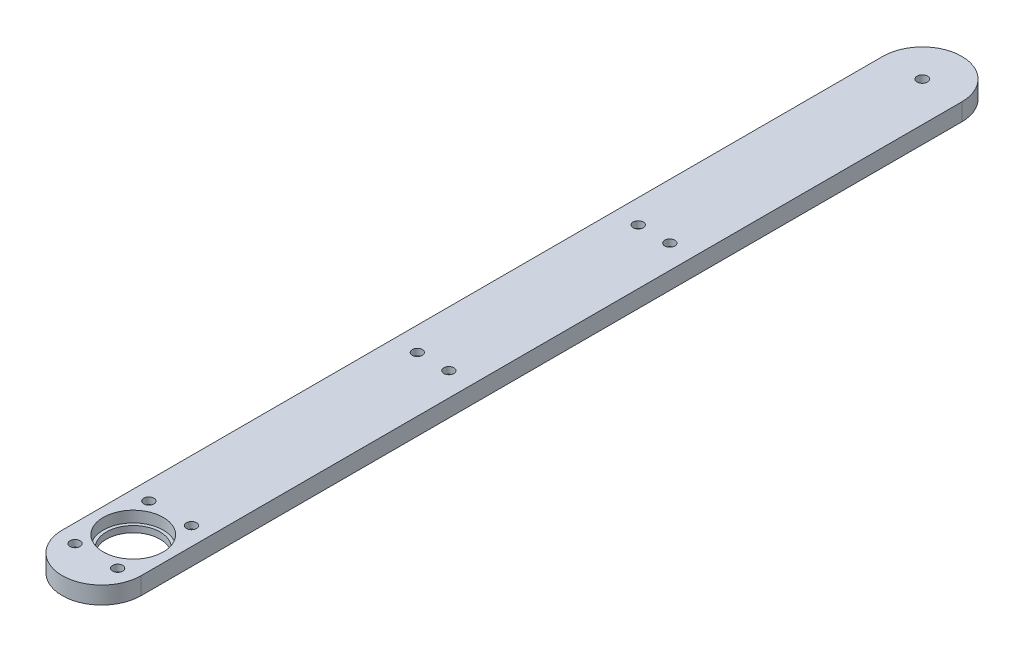
SolidWorks part; units mm, degrees
material "7075-T6 (SN)"
ref_plane "정면" through (0, 0, 0) normal (0, 0, 1) x (1, 0, 0)
ref_plane "윗면" through (0, 0, 0) normal (0, 1, 0) x (1, 0, 0)
ref_plane "우측면" through (0, 0, 0) normal (1, 0, 0) x (0, 0, -1)
sketch "스케치1" plane through (0, 0, 0) normal (0, 1, 0) x (1, 0, 0)
  circle A0 centre (0, 0) radius 5
  dimension "D1" = 10
extrude "보스-돌출1" add sketch "스케치1" along normal blind 10.5 and the other way blind 10.5
sketch "스케치6" plane through (0, 0, 0) normal (0, 1, 0) x (1, 0, 0)
  line L0 (-12.5, 0) -> (-12.5, -260)
  line L1 (0, 0) -> (0, -260) construction
  line L2 (12.5, 0) -> (12.5, -260)
  arc A0 (12.5, 0) -> (-12.5, 0) centre (0, 0) ccw
  arc A1 (-12.5, -260) -> (12.5, -260) centre (0, -260) ccw
  dimension "D1" = 25
  dimension "D3" = 25
  dimension "D2" = 260
extrude "보스-돌출3" add sketch "스케치6" along normal blind 4.5 and the other way blind 4.5
sketch "스케치7" plane through (0, -4.5, 0) normal (0, -1, 0) x (1, 0, 0)
  circle A0 centre (0, 0) radius 6
  dimension "D1" = 12
extrude "보스-돌출4" add sketch "스케치7" along normal blind 3
sketch "스케치8" plane through (0, 4.5, 0) normal (0, 1, 0) x (1, 0, 0)
  circle A0 centre (0, 0) radius 6
  dimension "D1" = 12
extrude "보스-돌출5" add sketch "스케치8" along normal blind 3
sketch "스케치9" plane through (0, -4.5, 0) normal (0, -1, 0) x (1, 0, 0)
  circle A0 centre (0, 250) radius 9.5
  dimension "D1" = 19
  dimension "D2" = 250
extrude "컷-돌출1" cut sketch "스케치9" against normal blind 7
sketch "스케치10" plane through (0, 2.5, 0) normal (0, -1, 0) x (1, 0, 0)
  circle A0 centre (0, 250) radius 8.5
  dimension "D1" = 17
  dimension "D2" = 250
extrude "컷-돌출2" cut sketch "스케치10" against normal through all
hole_wizard "M4 탭을 위한 탭 드릴1" positions "스케치21" profile "스케치17" hole size "M4" standard "ISO" end condition through all
sketch "스케치21" plane through (0, -10.5, 0) normal (0, -1, 0) x (-1, 0, 0)
  point P0 (0, 0)
sketch "스케치17" plane through (0, -10.5, 0) normal (1, 0, 0) x (0, 0, -1)
  line L0 (0, 0) -> (0, 21)
  line L1 (0, 21) -> (1.65, 21)
  line L2 (1.65, 21) -> (1.65, 0)
  line L5 (1.65, 0) -> (0, 0)
  line L11 (0, -6.35) -> (0, 107.95) construction
  dimension "관통 구멍 지름" = 3.3
  dimension "관통 구멍 깊이" = 21
sketch "스케치22" plane through (0, 0, 0) normal (0, 0, 1) x (1, 0, 0)
  line L0 (-28.7442, 0) -> (35.389, 0) construction
  line L1 (-23.3733, 1) -> (24.2836, 1)
  line L2 (-23.3733, 1) -> (-23.3733, 15.9087)
  line L3 (-23.3733, 15.9087) -> (24.2836, 15.9087)
  line L4 (24.2836, 1) -> (24.2836, 15.9087)
  line L5 (12.5, 4.5) -> (-12.5, 4.5) construction
  dimension "D1" = 1
extrude "컷-돌출3" cut sketch "스케치22" against normal mid plane 2222
sketch "스케치23" plane through (0, -4.5, 0) normal (0, -1, 0) x (1, 0, 0)
  circle A0 centre (0, 250) radius 9.5
  circle A1 centre (0, 250) radius 9.5 construction
  circle A2 centre (0, 250) radius 8.5
  dimension "D1" = 17
extrude "보스-돌출6" add sketch "스케치23" against normal blind 2
sketch "스케치24" plane through (0, -4.5, 0) normal (0, -1, 0) x (1, 0, 0)
  line L0 (-29.2668, 258.5) -> (36.6113, 258.5) construction
  line L1 (-28.2481, 272.5) -> (30.1593, 272.5) construction
  line L2 (0, 250) -> (-14.2884, 274.7482) construction
  line L3 (0, 279.9963) -> (0, 224.3546) construction
  circle A0 centre (0, 250) radius 13.5 construction
  circle A1 centre (0, 250) radius 8.5 construction
  arc A3 (12.5, 260) -> (-12.5, 260) centre (0, 260) ccw construction
  dimension "D1" = 27
  dimension "D2" = 30
hole_wizard "M3 육각 소켓 머리 캡 나사용 카운터보어1" positions "스케치27" profile "스케치26" counterbore size "M3" standard "ISO" end condition through all
sketch "스케치27" plane through (0, -4.5, 0) normal (0, -1, 0) x (-1, 0, 0)
  line L0 (0, -250) -> (14.2884, -274.7482) construction
  circle A0 centre (0, -250) radius 13.5 construction
  point P0 (6.75, -261.6913)
sketch "스케치26" plane through (-6.75, -4.5, 261.6913) normal (1, 0, 0) x (0, 0, -1)
  line L0 (0, 0) -> (0, 5.5)
  line L1 (0, 5.5) -> (1.6, 5.5)
  line L3 (1.6, 5.5) -> (1.6, 3.4)
  line L4 (1.6, 3.4) -> (3.25, 3.4)
  line L5 (3.25, 3.4) -> (3.25, 0)
  line L7 (3.25, 0) -> (0, 0)
  line L11 (0, -6.35) -> (0, 107.95) construction
  dimension "관통 구멍 지름" = 3.2
  dimension "관통 구멍 깊이" = 5.5
  dimension "카운터보어 지름" = 6.5
  dimension "카운터보어 깊이" = 3.4
pattern_circular "원형 패턴1" count 6 over 360 about axis through (0, -2.5, 250) along (0, -1, 0) skipping 1, 4 of "M3 육각 소켓 머리 캡 나사용 카운터보어1"
sketch "스케치28" plane through (0, -4.5, 0) normal (0, -1, 0) x (1, 0, 0)
  line L0 (-27.9315, 15) -> (43.3351, 15) construction
  line L1 (-5, 31.6742) -> (-5, -25.3392) construction
  line L2 (0, 41.1764) -> (0, -28.9025) construction
  line L3 (-19.0232, 0) -> (34.8722, 0) construction
  dimension "D1" = 5
  dimension "D2" = 15
hole_wizard "M3 육각 소켓 머리 캡 나사용 카운터보어2" positions "스케치29" profile "스케치30" counterbore size "M3" standard "ISO" end condition through all
sketch "스케치29" plane through (0, -4.5, 0) normal (0, -1, 0) x (-1, 0, 0)
  line L0 (27.9315, -15) -> (-43.3351, -15) construction
  line L1 (5, -31.6742) -> (5, 25.3392) construction
  point P0 (5, -15)
sketch "스케치30" plane through (-5, -4.5, 15) normal (1, 0, 0) x (0, 0, -1)
  line L0 (0, 0) -> (0, 5.5)
  line L1 (0, 5.5) -> (1.6, 5.5)
  line L3 (1.6, 5.5) -> (1.6, 3.4)
  line L4 (1.6, 3.4) -> (3.25, 3.4)
  line L5 (3.25, 3.4) -> (3.25, 0)
  line L7 (3.25, 0) -> (0, 0)
  line L11 (0, -6.35) -> (0, 107.95) construction
  dimension "관통 구멍 지름" = 3.2
  dimension "관통 구멍 깊이" = 5.5
  dimension "카운터보어 지름" = 6.5
  dimension "카운터보어 깊이" = 3.4
pattern_linear "선형 패턴1" count 3 spacing 70 along (0, 0, 1) count 2 spacing 10 along (1, 0, 0) of "M3 육각 소켓 머리 캡 나사용 카운터보어2"
sketch "스케치31" plane through (0, -4.5, 0) normal (0, -1, 0) x (1, 0, 0)
  circle A0 centre (5, 15) radius 3.25
  circle A1 centre (5, 15) radius 3.25 construction
  circle A2 centre (-5, 15) radius 3.25
  circle A3 centre (-5, 15) radius 3.25 construction
extrude "보스-돌출7" add sketch "스케치31" against normal blind 5.5
